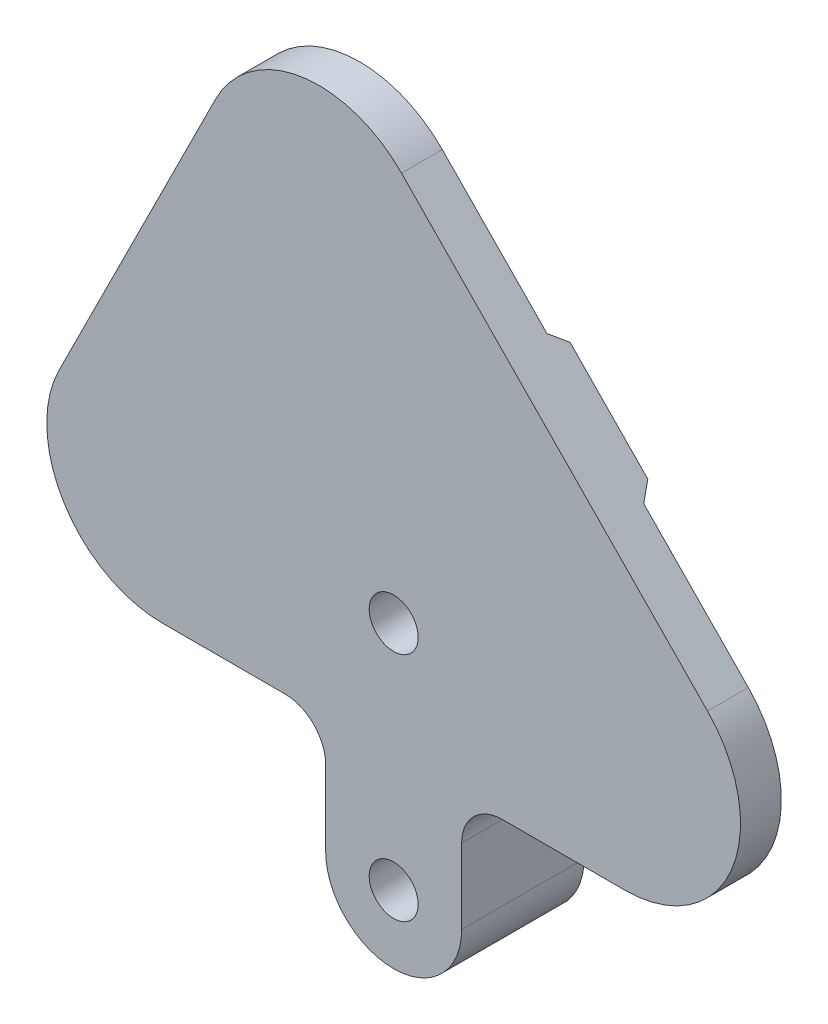
SolidWorks part; units mm, degrees
material "ABS"
ref_plane "Płaszczyzna przednia" through (0, 0, 0) normal (0, 0, 1) x (1, 0, 0)
ref_plane "Płaszczyzna górna" through (0, 0, 0) normal (0, 1, 0) x (1, 0, 0)
ref_plane "Płaszczyzna prawa" through (0, 0, 0) normal (1, 0, 0) x (0, 0, -1)
sketch "Szkic1" plane through (0, 0, 0) normal (0, 0, 1) x (1, 0, 0)
  line L0 (-7.6026, 3.8013) -> (3.8974, 26.8013)
  line L1 (17.5761, 28.944) -> (40.0761, 5.944)
  line L2 (34, -8.5) -> (25, -8.5)
  line L3 (22, -17) -> (22, -11.5)
  line L4 (12, -17) -> (12, -11.5)
  line L5 (9, -8.5) -> (0, -8.5)
  arc A0 (-7.6026, 3.8013) -> (0, -8.5) centre (0, 0) ccw
  arc A1 (17.5761, 28.944) -> (3.8974, 26.8013) centre (11.5, 23) ccw
  arc A2 (34, -8.5) -> (40.0761, 5.944) centre (34, 0) ccw
  circle A3 centre (17, 0) radius 1.8
  circle A4 centre (17, -17) radius 1.8
  arc A5 (12, -17) -> (22, -17) centre (17, -17) ccw
  arc A6 (12, -11.5) -> (9, -8.5) centre (9, -11.5) ccw
  arc A7 (22, -11.5) -> (25, -8.5) centre (25, -11.5) cw
  point P20 (12, -8.5)
  dimension "D1" = 17
  dimension "D2" = 17
  dimension "D3" = 3.6
  dimension "D4" = 34
  dimension "D5" = 17
  dimension "D6" = 23
  dimension "D7" = 17
  dimension "D8" = 11.5
  dimension "D10" = 23
  dimension "D11" = 17
  dimension "D12" = 3.6
  dimension "D14" = 5
  dimension "D15" = 3
  dimension "D9" = 23
  dimension "D13" = 17
extrude "Dodanie-wyciągnięcie1" add sketch "Szkic1" along normal blind 3
sketch "Szkic2" plane through (0, 0, 0) normal (0, 0, -1) x (-1, 0, 0)
  circle A0 centre (-34, 0) radius 4
  circle A1 centre (-11.5, 23) radius 4
  circle A2 centre (0, 0) radius 4
  dimension "D1" = 8
  dimension "D2" = 8
  dimension "D3" = 8
extrude "Wytnij-wyciągnięcie1" cut sketch "Szkic2" against normal blind 2
chamfer "Sfazowanie1" distance 0.5 angle 45 3 edges at (7.5, 23, 2) (-4, 0, 2) (30, 0, 2)
sketch "Szkic3" plane through (0, 0, 0) normal (0, 0, -1) x (-1, 0, 0)
  line L2 (-22, -17) -> (-22, 3.786)
  line L3 (-22.9021, 5.9305) -> (-31.6846, 14.522)
  line L4 (-25.9676, 20.366) -> (-16.0643, 10.678)
  line L5 (-40.0761, 5.944) -> (-17.5761, 28.944) construction
  line L6 (1.022, 16.9626) -> (-12.6248, 10.1392)
  line L7 (-3.8974, 26.8013) -> (7.6026, 3.8013) construction
  line L8 (2.6833, 13.64) -> (-10.3416, 7.1276)
  line L9 (-12, -17) -> (-12, 4.4443)
  line L10 (1.022, 16.9626) -> (2.6833, 13.64)
  line L11 (-25.9676, 20.366) -> (-31.6846, 14.522)
  arc A0 (-22, -17) -> (-12, -17) centre (-17, -17) ccw
  circle A2 centre (-17, 0) radius 1.8
  circle A3 centre (-17, -17) radius 1.8
  circle A4 centre (-34, 0) radius 3.5 construction
  circle A5 centre (-11.5, 23) radius 3.5 construction
  circle A6 centre (0, 0) radius 3.5 construction
  arc A7 (-10.3416, 7.1276) -> (-12, 4.4443) centre (-9, 4.4443) ccw
  arc A8 (-12.6248, 10.1392) -> (-16.0643, 10.678) centre (-13.9665, 12.8225) cw
  arc A9 (-22, 3.786) -> (-22.9021, 5.9305) centre (-25, 3.786) ccw
  dimension "D1" = 10
  dimension "D3" = 12
  dimension "D2" = 12
  dimension "D4" = 11
  dimension "D9" = 3
  dimension "D5" = 11
  dimension "D6" = 90
  dimension "D7" = 90
  dimension "D8" = 90
extrude "Dodanie-wyciągnięcie2" add sketch "Szkic3" along normal blind 1
chamfer "Sfazowanie2" distance 1 angle 45 9 edges at (12, -3.5279, 0) (22, -3.857, 0) (27.2933, 10.2262, 0) (22.2347, 4.9492, 0) (5.8014, 13.5509, 0) (14.4307, 9.8586, 0) (21.016, 15.522, 0) (3.8292, 10.3838, 0) (11.552, 6.0215, 0)
sketch "Szkic4" plane through (0, 0, -1) normal (0, 0, -1) x (-1, 0, 0)
  line L0 (-22, -12.1) -> (-12, -12.1)
  line L1 (-22, -12.1) -> (-22, -17)
  line L3 (-12, -12.1) -> (-12, -17)
  arc A0 (-22, -17) -> (-12, -17) centre (-17, -17) ccw
  circle A1 centre (-17, -17) radius 1.8
  dimension "D1" = 10
  dimension "D2" = 4.9
  dimension "D3" = 10
extrude "Dodanie-wyciągnięcie3" add sketch "Szkic4" along normal blind 5
